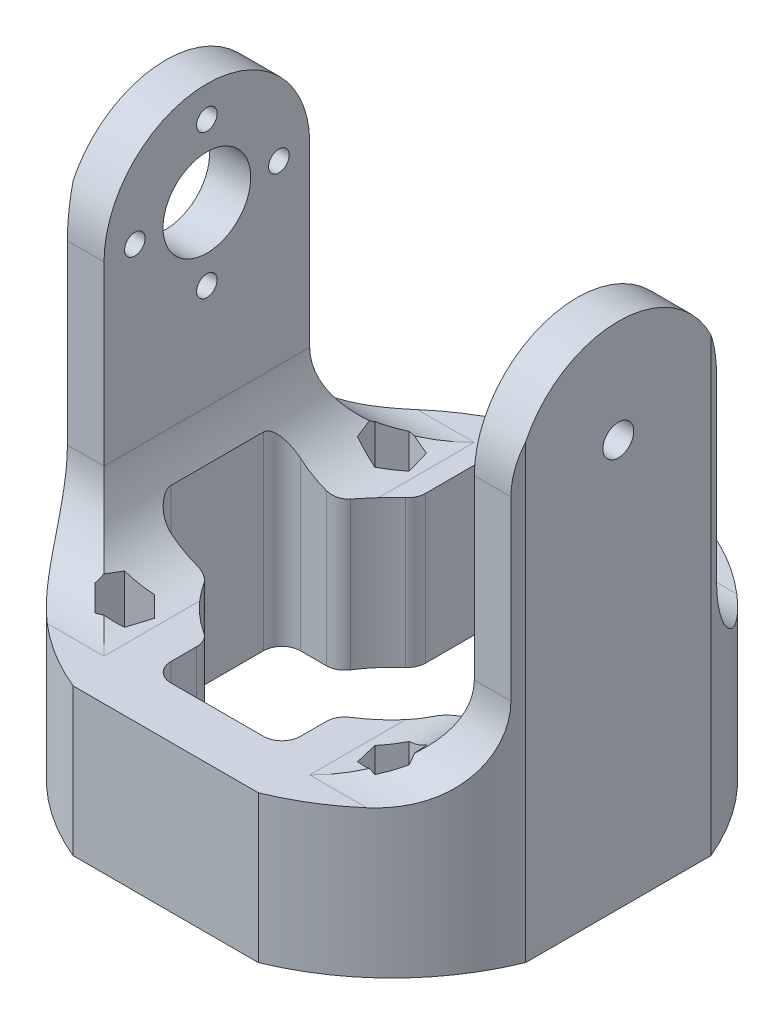
SolidWorks part; units mm, degrees
material "eSUN Tough Resin"
ref_plane "Front Plane" through (0, 0, 0) normal (0, 0, 1) x (1, 0, 0)
ref_plane "Top Plane" through (0, 0, 0) normal (0, 1, 0) x (1, 0, 0)
ref_plane "Right Plane" through (0, 0, 0) normal (1, 0, 0) x (0, 0, -1)
sketch "Sketch2" plane through (0, 0, 0) normal (0, 1, 0) x (1, 0, 0)
  line L0 (17, -17) -> (-17, -17)
  line L1 (17, -17) -> (17, 17)
  line L2 (17, 17) -> (-17, 17)
  line L3 (-17, -17) -> (-17, 17)
  line L4 (-4.5, -19.5) -> (-1.5, -19.5) construction
  line L5 (-1.5, -19.5) -> (1.5, -19.5) construction
  line L6 (-22, -22) -> (22, -22)
  line L7 (-10.5, 13) -> (-10.5, 17)
  line L8 (-13, 10.5) -> (-17, 10.5)
  line L9 (-10.5, -13) -> (-10.5, -17)
  line L10 (-13, -10.5) -> (-17, -10.5)
  line L11 (10.5, -13) -> (10.5, -17)
  line L12 (13, -10.5) -> (17, -10.5)
  line L13 (13, 10.5) -> (17, 10.5)
  line L14 (10.5, 13) -> (10.5, 17)
  line L15 (-22, -22) -> (-22, 22)
  line L16 (-22, 22) -> (22, 22)
  line L17 (22, -22) -> (22, 22)
  line L18 (-22, -22) -> (22, 22) construction
  line L19 (-22, 22) -> (22, -22) construction
  line L20 (1.5, -19.5) -> (4.5, -19.5) construction
  line L21 (-19.5, 4.5) -> (-19.5, 1.5) construction
  line L22 (-19.5, 1.5) -> (-19.5, -1.5) construction
  line L23 (-19.5, -1.5) -> (-19.5, -4.5) construction
  line L24 (19.5, 4.5) -> (19.5, 1.5) construction
  line L25 (19.5, 1.5) -> (19.5, -1.5) construction
  line L26 (19.5, -1.5) -> (19.5, -4.5) construction
  line L27 (21.3, 4.5) -> (21.3, -4.5)
  line L28 (17.7, 4.5) -> (17.7, -4.5)
  line L29 (-17.7, 4.5) -> (-17.7, -4.5)
  line L31 (-21.3, 4.5) -> (-21.3, -4.5)
  line L32 (-4.5, -17.7) -> (4.5, -17.7)
  line L33 (-4.5, -21.3) -> (4.5, -21.3)
  line L38 (8.0816, -10.5) -> (8.0816, 22)
  line L39 (-8.0816, -10.5) -> (-8.0816, 22)
  line L40 (19.5, 6.3) -> (11.6564, 6.3)
  line L41 (19.5, -6.3) -> (11.6564, -6.3)
  line L42 (6.3, -19.5) -> (6.3, -11.6564)
  line L43 (-6.3, -19.5) -> (-6.3, -11.6564)
  line L44 (-19.5, -6.3) -> (-11.6564, -6.3)
  line L45 (-19.5, 6.3) -> (-11.6564, 6.3)
  line L46 (-11.6564, 6.3) -> (-11.6564, -6.3)
  line L47 (11.6564, 6.3) -> (11.6564, -6.3)
  line L48 (-6.3, -11.6564) -> (6.3, -11.6564)
  circle A3 centre (0, 0) radius 13.25
  circle A4 centre (-13, 13) radius 1.125
  circle A5 centre (13, 13) radius 1.125
  circle A6 centre (13, -13) radius 1.125
  circle A7 centre (-13, -13) radius 1.125
  arc A8 (10.5, 13) -> (13, 10.5) centre (13, 13) ccw
  arc A9 (13, -10.5) -> (10.5, -13) centre (13, -13) ccw
  arc A10 (-10.5, -13) -> (-13, -10.5) centre (-13, -13) ccw
  arc A11 (-13, 10.5) -> (-10.5, 13) centre (-13, 13) ccw
  circle A12 centre (0, 0) radius 19.9812
  arc A13 (9, 22) -> (22, 9) centre (0, 0) cw
  arc A14 (22, -9) -> (9, -22) centre (0, 0) cw
  arc A15 (-9, -22) -> (-22, -9) centre (0, 0) cw
  arc A16 (-22, 9) -> (-9, 22) centre (0, 0) cw
  circle A20 centre (0, -7.75) radius 1.5
  circle A21 centre (0, 19.06) radius 1.5
  arc A54 (4.5, -17.7) -> (4.5, -21.3) centre (4.5, -19.5) cw
  arc A55 (-4.5, -17.7) -> (-4.5, -21.3) centre (-4.5, -19.5) ccw
  arc A60 (-17.7, 4.5) -> (-21.3, 4.5) centre (-19.5, 4.5) ccw
  arc A61 (-17.7, -4.5) -> (-21.3, -4.5) centre (-19.5, -4.5) cw
  arc A70 (21.3, 4.5) -> (17.7, 4.5) centre (19.5, 4.5) ccw
  arc A71 (21.3, -4.5) -> (17.7, -4.5) centre (19.5, -4.5) cw
  point P25 (0, 0)
  point P68 (-22, 0)
  point P91 (0, -21.3)
  point P92 (0, -22)
  point P93 (-21.3, 0)
  point P98 (21.3, 0)
  point P100 (22, 0)
  dimension "D2" = 2.25
  dimension "D3" = 26
  dimension "D5" = 26.5
  dimension "D6" = 2.5
  dimension "D9" = 23.7697
  dimension "D20" = 39.9625
  dimension "D21" = 3
  dimension "D14" = 1.8
  dimension "D1" = 34
  dimension "D7" = 44
  dimension "D8" = 18
  dimension "D10" = 18
  dimension "D13" = 3
  dimension "D15" = 2.5
  dimension "D16" = 2.5
  dimension "D17" = 2.5
  dimension "D18" = 9
  dimension "D22" = 7.75
  dimension "D23" = 26.81
extrude "Boss-Extrude1" add sketch "Sketch2" along normal blind 14.3 contours L44 A61 L31 A60 L45 A12 L3 A16 L15 A15 | A16 L3 A12 L2 | A16 L2 A12 L39 L16 | A15 L0 A12 L3 | A55 L43 A12 L0 A15 L6 A14 L42 A54 L33 | A14 L1 A12 L0 | L27 A71 L41 A12 L1 A14 L17 A13 L40 A70 | L40 A12 L1 | L1 A12 L41 | A8 L14 L2 L38 A3 L40 L1 L13 | A9 L12 L1 L41 A3 L42 L0 L11 | L11 A12 L12 A9 A6 | L42 A12 L0 | A10 L9 L0 L43 A3 L44 L3 L10 | L0 A12 L43 | L10 A12 L9 A10 A7 | L44 A12 L3 | L3 A12 L45 | A11 L8 L3 L45 A3 L39 L2 L7 | L7 A12 L8 A11 A4 | L13 A12 L14 A8 A5 | A13 L16 L38 A12 L2 | A13 L2 A12 L1 | L39 A12 L2 | L2 A12 L38 | A71 L27 A70 A12 | A71 A12 A70 L28 | A12 A71 L28 A70 L40 L1 L41 | A70 L40 A12 | L41 A71 A12 | A61 A12 A60 L31 | A60 A12 L45 | L29 A61 A12 L44 L3 L45 A60 | A61 L29 A60 A12 | A12 A61 L44 | A55 L32 A54 A12 L42 L0 L43 | A55 A12 L43 | L32 A55 A12 A54 | A12 A55 L33 A54 | A12 A54 L42 region at (12.8639, 0, 19.5872) region at (14.9975, 0, 14.9975) region at (17.336, 0, 13.5566) region at (7.7665, 0, 17.6886) region at (11.0948, 0, 11.0948) region at (10.5919, 0, 15) region at (17.6886, 0, 7.7665) region at (0, 0, 17.448) region at (6.2775, 0, 19.1053) region at (17.448, 0, 0) region at (19.1053, 0, 6.2775) region at (-7.7665, 0, 17.6886) region at (-11.0948, 0, 11.0948) region at (0, 0, 20.4143) region at (0, 0, 18.7323) region at (-14.9975, 0, 14.9975) region at (11.9796, 0, -10.4208) region at (17.6886, 0, -7.7665) region at (20.4143, 0, 0) region at (18.7323, 0, 0) region at (14.9975, 0, -14.9975) region at (-14.0639, 0, 14.0639) region at (-6.2775, 0, 19.1053) region at (-21.664, 0, 0) region at (15, 0, -10.5919) region at (19.1053, 0, -6.2775) region at (11.3015, 0, -19.0092) region at (-17.6886, 0, 7.7665) region at (8.9093, 0, -17.4367) region at (-17.448, 0, 0) region at (-19.1053, 0, 6.2775) region at (-11.9796, 0, -10.4208) region at (-14.9975, 0, -14.9975) region at (-11.3015, 0, -19.0092) region at (-17.6886, 0, -7.7665) region at (-20.4143, 0, 0) region at (-18.7323, 0, 0) region at (-8.9093, 0, -17.4367) region at (-14.0639, 0, -14.0639) region at (-19.1053, 0, -6.2775)
fillet "Fillet1" radius 1.8 14 edges at (-11.6564, 7.15, -6.3) (11.6564, 7.15, -6.3) (6.3, 7.15, 11.6564) (11.6564, 7.15, 6.3) (-11.6564, 7.15, 6.3) (-6.3, 7.15, 11.6564) (-6.3, 7.15, 17) (6.3, 7.15, 17) (17, 7.15, 6.3) (17, 7.15, -6.3) (-17, 7.15, -6.3) (-17, 7.15, 6.3) (8.0816, 7.15, -10.5) (-8.0816, 7.15, -10.5)
sketch "Sketch4" plane through (22, 0, 0) normal (1, 0, 0) x (0, 0, -1)
  line L0 (-10, 0) -> (-10, 39.5)
  line L1 (10, 0) -> (10, 39.5)
  line L2 (-10, 0) -> (10, 0)
  line L4 (-9, 14.3) -> (9, 14.3) construction
  line L9 (9, 0) -> (22, 0) construction
  arc A0 (-10, 39.5) -> (10, 39.5) centre (0, 39.5) cw
  circle A9 centre (0, 39.5) radius 1.5
  circle A10 centre (0, 39.5) radius 4.5
  circle A11 centre (0, 39.5) radius 3
  line M14 (9, 0) -> (9, 14.3)
  line M15 (9, 14.3) -> (-9, 14.3)
  line M16 (-9, 14.3) -> (-9, 0)
  dimension "D1" = 3
  dimension "D2" = 6
  dimension "D5" = 20
  dimension "D4" = 9
  dimension "D3" = 25.2
sketch "Sketch5" plane through (-22, 0, 0) normal (-1, 0, 0) x (0, 0, 1)
  line L0 (-10, 0) -> (-10, 39.5)
  line L1 (10, 0) -> (10, 39.5)
  line L2 (-10, 0) -> (10, 0)
  line L3 (0, 46.5) -> (0, 39.5) construction
  line L4 (0, 39.5) -> (0, 32.5) construction
  line L5 (0, 39.5) -> (-7, 39.5) construction
  line L6 (0, 39.5) -> (7, 39.5) construction
  line L7 (-10, 0) -> (-10, 39.5) construction
  arc A0 (-10, 39.5) -> (10, 39.5) centre (0, 39.5) cw
  circle A1 centre (0, 46.5) radius 1
  circle A2 centre (7, 39.5) radius 1
  circle A3 centre (-7, 39.5) radius 1
  circle A4 centre (0, 32.5) radius 1
  circle A5 centre (0, 39.5) radius 4.2646
  dimension "D1" = 8.5292
  dimension "D2" = 2
  dimension "D3" = 7
  dimension "D4" = 20
  dimension "D5" = 25.2
extrude "Boss-Extrude2" add sketch "Sketch5" against normal blind 4
extrude "Boss-Extrude3" add sketch "Sketch4" against normal blind 4 contours A0 L0 L2 L1 A10 M16 M15 M14 | A10 A11 | A11 A9 region at (22, 28.9436, 0) region at (22, 39.5, 4.3727) region at (22, 39.5, 2.9151)
extrude "Cut-Extrude1" cut sketch "Sketch2<11>" along normal blind 72.095 contours L6 A15 L0 L3 L15 | L15 A16 L3 L2 L16 | L17 A14 L1 L0 L6 | L16 A13 L2 L1 L17 region at (18.2769, 0, 18.2769) region at (-18.2769, 0, 18.2769) region at (18.2769, 0, -18.2769) region at (-18.2769, 0, -18.2769)
sketch "Sketch2<11>" plane through (0, 0, 0) normal (0, 1, 0) x (1, 0, 0) same geometry as "Sketch2"
sketch "Sketch6" plane through (0, 14.3, 0) normal (0, 1, 0) x (1, 0, 0)
  line L7 (15.2865, 13.6127) -> (13.6127, 15.2865)
  line L8 (13.6127, 15.2865) -> (11.3262, 14.6738)
  line L9 (11.3262, 14.6738) -> (10.7135, 12.3873)
  line L10 (10.7135, 12.3873) -> (12.3873, 10.7135)
  line L11 (12.3873, 10.7135) -> (14.6738, 11.3262)
  line L12 (14.6738, 11.3262) -> (15.2865, 13.6127)
  line L13 (12.3873, -10.7135) -> (10.7135, -12.3873)
  line L14 (10.7135, -12.3873) -> (11.3262, -14.6738)
  line L15 (11.3262, -14.6738) -> (13.6127, -15.2865)
  line L16 (13.6127, -15.2865) -> (15.2865, -13.6127)
  line L17 (15.2865, -13.6127) -> (14.6738, -11.3262)
  line L18 (14.6738, -11.3262) -> (12.3873, -10.7135)
  line L19 (-10.7135, -12.3873) -> (-12.3873, -10.7135)
  line L20 (-12.3873, -10.7135) -> (-14.6738, -11.3262)
  line L21 (-14.6738, -11.3262) -> (-15.2865, -13.6127)
  line L22 (-15.2865, -13.6127) -> (-13.6127, -15.2865)
  line L23 (-13.6127, -15.2865) -> (-11.3262, -14.6738)
  line L24 (-11.3262, -14.6738) -> (-10.7135, -12.3873)
  line L25 (-13.6127, 15.2865) -> (-15.2865, 13.6127)
  line L26 (-15.2865, 13.6127) -> (-14.6738, 11.3262)
  line L27 (-14.6738, 11.3262) -> (-12.3873, 10.7135)
  line L28 (-12.3873, 10.7135) -> (-10.7135, 12.3873)
  line L29 (-10.7135, 12.3873) -> (-11.3262, 14.6738)
  line L30 (-11.3262, 14.6738) -> (-13.6127, 15.2865)
  circle A4 centre (-13, 13) radius 2.05 construction
  circle A5 centre (13, 13) radius 2.05 construction
  circle A6 centre (13, -13) radius 2.05 construction
  circle A7 centre (-13, -13) radius 2.05 construction
  dimension "D1" = 4.1
extrude "Cut-Extrude2" cut sketch "Sketch6" against normal blind 5
fillet "Fillet2" radius 8 6 edges at (-19.7819, 14.3, -10) (-19.7819, 14.3, 10) (19.7819, 14.3, 10) (19.7819, 14.3, -10) (-18, 14.3, 0) (18, 14.3, 0)
extrude "Boss-Extrude4" add sketch "Sketch4<3>" against normal blind 6.8 contours A11 A9 | A10 A11 region at (22, 39.5, 4.3727) region at (22, 39.5, 2.9151)
sketch "Sketch4<3>" plane through (22, 0, 0) normal (1, 0, 0) x (0, 0, -1) same geometry as "Sketch4"
chamfer "Chamfer1" distance 1.6 angle 45 1 edges at (15.2, 39.5, -4.5)
